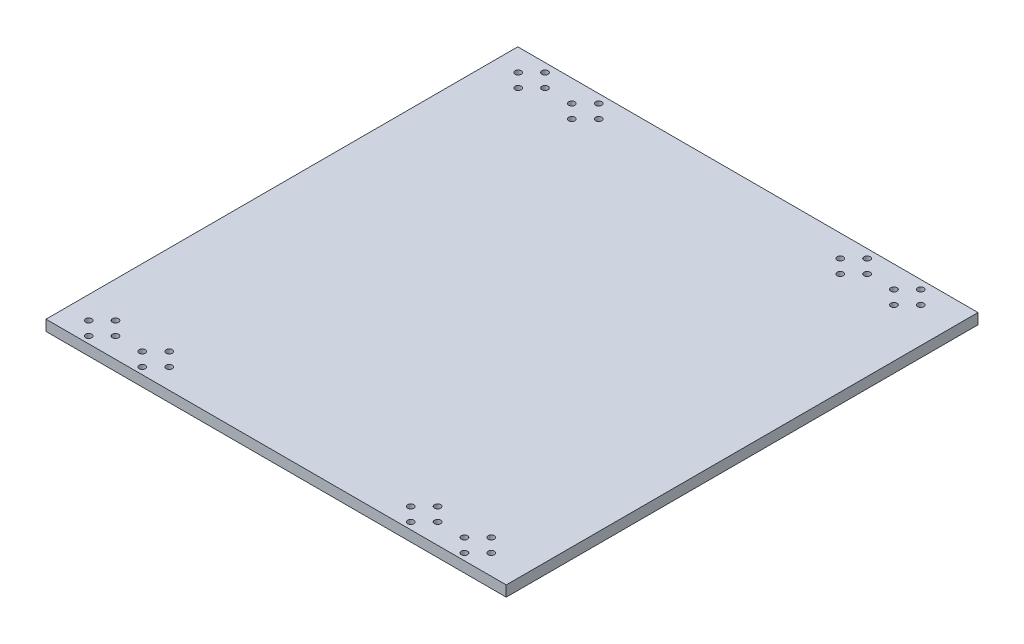
SolidWorks part; units mm, degrees
ref_plane "Front Plane" through (0, 0, 0) normal (0, 0, 1) x (1, 0, 0)
ref_plane "Top Plane" through (0, 0, 0) normal (0, 1, 0) x (1, 0, 0)
ref_plane "Right Plane" through (0, 0, 0) normal (1, 0, 0) x (0, 0, -1)
sketch "Sketch1" plane through (0, 0, 0) normal (0, 1, 0) x (1, 0, 0)
  line L1 (-132.0925, 92.3972) -> (142.2275, 92.3972)
  line L2 (-132.0925, 92.3972) -> (-132.0925, -195.6388)
  line L3 (-132.0925, -195.6388) -> (142.2275, -195.6388)
  line L4 (142.2275, 92.3972) -> (142.2275, -195.6388)
  dimension "D1" = 274.32
  dimension "D2" = 288.036
extrude "Boss-Extrude1" add sketch "Sketch1" along normal blind 6.35
sketch "Sketch2" plane through (0, 0, 0) normal (0, -1, 0) x (1, 0, 0)
  circle A0 centre (121.2775, -75.5428) radius 1.85 construction
  circle A1 centre (105.2775, -75.5428) radius 1.85 construction
  circle A2 centre (113.2775, -83.5428) radius 1.85 construction
  circle A3 centre (113.2775, -67.5428) radius 1.85 construction
  circle A4 centre (121.2775, -75.5428) radius 1.85
  circle A5 centre (105.2775, -75.5428) radius 1.85
  circle A6 centre (113.2775, -83.5428) radius 1.85
  circle A7 centre (113.2775, -67.5428) radius 1.85
  circle A8 centre (89.2775, -75.5428) radius 1.85 construction
  circle A9 centre (89.2775, -75.5428) radius 1.85
  circle A10 centre (81.2775, -83.5428) radius 1.85 construction
  circle A11 centre (81.2775, -83.5428) radius 1.85
  circle A12 centre (81.2775, -67.5428) radius 1.85 construction
  circle A13 centre (81.2775, -67.5428) radius 1.85
  circle A14 centre (73.2775, -75.5428) radius 1.85 construction
  circle A15 centre (73.2775, -75.5428) radius 1.85
  circle A16 centre (-86.7225, -75.5428) radius 1.85 construction
  circle A17 centre (-118.7225, -75.5428) radius 1.85 construction
  circle A18 centre (-110.7225, -83.5428) radius 1.85 construction
  circle A19 centre (-102.7225, -75.5428) radius 1.85 construction
  circle A20 centre (-110.7225, -67.5428) radius 1.85 construction
  circle A21 centre (-86.7225, -75.5428) radius 1.85
  circle A22 centre (-118.7225, -75.5428) radius 1.85
  circle A23 centre (-110.7225, -83.5428) radius 1.85
  circle A24 centre (-102.7225, -75.5428) radius 1.85
  circle A25 centre (-110.7225, -67.5428) radius 1.85
  circle A26 centre (-70.7225, -75.5428) radius 1.85 construction
  circle A27 centre (-78.7225, -67.5428) radius 1.85 construction
  circle A28 centre (-78.7225, -83.5428) radius 1.85 construction
  circle A29 centre (-86.7225, -75.5428) radius 1.85
  circle A30 centre (-70.7225, -75.5428) radius 1.85
  circle A31 centre (-78.7225, -67.5428) radius 1.85
  circle A32 centre (-78.7225, -83.5428) radius 1.85
  circle A33 centre (73.2775, 180.4572) radius 1.85 construction
  circle A34 centre (81.2775, 188.4572) radius 1.85 construction
  circle A35 centre (81.2775, 172.4572) radius 1.85 construction
  circle A36 centre (89.2775, 180.4572) radius 1.85 construction
  circle A37 centre (105.2775, 180.4572) radius 1.85 construction
  circle A38 centre (113.2775, 188.4572) radius 1.85 construction
  circle A39 centre (121.2775, 180.4572) radius 1.85 construction
  circle A40 centre (113.2775, 172.4572) radius 1.85 construction
  circle A41 centre (73.2775, 180.4572) radius 1.85
  circle A42 centre (81.2775, 188.4572) radius 1.85
  circle A43 centre (81.2775, 172.4572) radius 1.85
  circle A44 centre (89.2775, 180.4572) radius 1.85
  circle A45 centre (105.2775, 180.4572) radius 1.85
  circle A46 centre (113.2775, 188.4572) radius 1.85
  circle A47 centre (121.2775, 180.4572) radius 1.85
  circle A48 centre (113.2775, 172.4572) radius 1.85
  circle A49 centre (-70.7225, 180.4572) radius 1.85 construction
  circle A50 centre (-78.7225, 188.4572) radius 1.85 construction
  circle A51 centre (-78.7225, 172.4572) radius 1.85 construction
  circle A52 centre (-86.7225, 180.4572) radius 1.85 construction
  circle A53 centre (-102.7225, 180.4572) radius 1.85 construction
  circle A54 centre (-110.7225, 188.4572) radius 1.85 construction
  circle A55 centre (-118.7225, 180.4572) radius 1.85 construction
  circle A56 centre (-110.7225, 172.4572) radius 1.85 construction
  circle A57 centre (-70.7225, 180.4572) radius 1.85
  circle A58 centre (-78.7225, 188.4572) radius 1.85
  circle A59 centre (-78.7225, 172.4572) radius 1.85
  circle A60 centre (-86.7225, 180.4572) radius 1.85
  circle A61 centre (-102.7225, 180.4572) radius 1.85
  circle A62 centre (-110.7225, 188.4572) radius 1.85
  circle A63 centre (-118.7225, 180.4572) radius 1.85
  circle A64 centre (-110.7225, 172.4572) radius 1.85
extrude "Cut-Extrude1" cut sketch "Sketch2" against normal up to next contours A22 | A23 | A25 | A24 | A21 | A31 | A32 | A30
extrude "Cut-Extrude2" cut sketch "Sketch2<5>" against normal up to next contours A15 | A13 | A11 | A9 | A5 | A7 | A4 | A6 | A42 | A41 | A43 | A44 | A45 | A46 | A48 | A47 | A63 | A64 | A62 | A61 | A60 | A58 | A59 | A57
sketch "Sketch2<5>" plane through (0, 0, 0) normal (0, -1, 0) x (1, 0, 0) same geometry as "Sketch2"
sketch "Sketch3" plane through (0, 0, 0) normal (0, -1, 0) x (1, 0, 0)
  line L0 (142.2275, 195.6388) -> (142.2275, -92.3972) construction
  line L1 (-132.0925, 195.6388) -> (142.2275, 195.6388)
  line L2 (-132.0925, 195.6388) -> (-132.0925, 192.4927)
  line L3 (-132.0925, 192.4927) -> (142.2275, 192.4927)
  line L4 (142.2275, 195.6388) -> (142.2275, 192.4927)
  line L6 (-132.0925, -92.3972) -> (142.2275, -92.3972)
  line L7 (-132.0925, -92.3972) -> (-132.0925, -88.7015)
  line L8 (-132.0925, -88.7015) -> (142.2275, -88.7015)
  line L9 (142.2275, -92.3972) -> (142.2275, -88.7015)
extrude "Cut-Extrude3" cut sketch "Sketch3" against normal up to next
